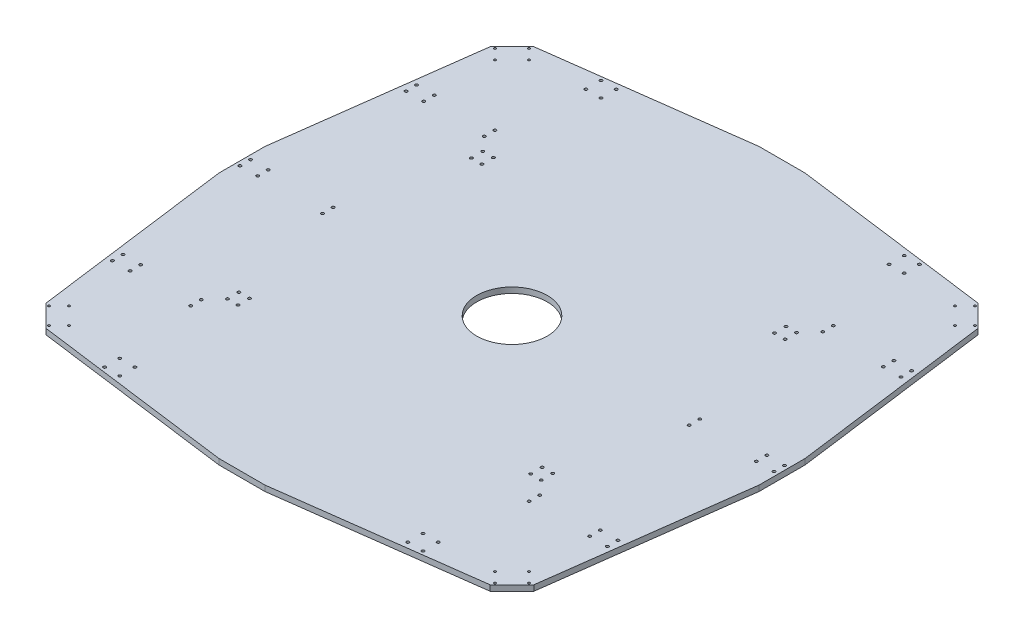
SolidWorks part; units mm, degrees
ref_plane "前视基准面" through (0, 0, 0) normal (0, 0, 1) x (1, 0, 0)
ref_plane "上视基准面" through (0, 0, 0) normal (0, 1, 0) x (1, 0, 0)
ref_plane "右视基准面" through (0, 0, 0) normal (1, 0, 0) x (0, 0, -1)
other "Configuration Table"
sketch "草图1" plane through (0, 0, 0) normal (0, 1, 0) x (1, 0, 0)
  line L0 (-314.9222, 345.9222) -> (-345.9222, 314.9222)
  line L5 (325, -325) -> (-325, 325) construction
  line L6 (325, 325) -> (-325, -325) construction
  line L7 (0, 325) -> (0, -325) construction
  line L8 (-325, 0) -> (325, 0) construction
  line L9 (314.9222, 345.9222) -> (32.7201, 383.0748)
  line L10 (314.9222, 345.9222) -> (345.9222, 314.9222)
  line L12 (-314.9222, 345.9222) -> (-32.7201, 383.0748)
  line L13 (0, 325) -> (0, 399.6983)
  line L14 (-32.7201, 383.0748) -> (32.7201, 383.0748)
  line L15 (314.9222, -345.9222) -> (32.7201, -383.0748)
  line L16 (-32.7201, -383.0748) -> (32.7201, -383.0748)
  line L17 (-314.9222, -345.9222) -> (-32.7201, -383.0748)
  line L18 (-314.9222, -345.9222) -> (-345.9222, -314.9222)
  line L19 (-345.9222, 314.9222) -> (-383.0748, 32.7201)
  line L20 (-383.0748, -32.7201) -> (-383.0748, 32.7201)
  line L21 (-345.9222, -314.9222) -> (-383.0748, -32.7201)
  line L22 (-345.9222, -314.9222) -> (-314.9222, -345.9222)
  line L23 (345.9222, -314.9222) -> (314.9222, -345.9222)
  line L24 (345.9222, -314.9222) -> (383.0748, -32.7201)
  line L25 (383.0748, 32.7201) -> (383.0748, -32.7201)
  line L26 (345.9222, 314.9222) -> (383.0748, 32.7201)
  line L27 (-337.8712, -313.8296) -> (-342.443, -318.4014)
  line L28 (-314.9222, -345.9222) -> (-293.6978, -324.6978)
  line L29 (-326.1795, -302.1379) -> (-298.6587, -329.6587)
  line L30 (-345.9222, -314.9222) -> (-325, -294)
  line L31 (-326.1795, -302.1379) -> (-329.6587, -298.6587)
  line L32 (-313.4871, -289.4455) -> (-337.8712, -313.8296)
  line L33 (-289.4455, -313.4871) -> (-313.8296, -337.8712)
  line L34 (-313.8296, -337.8712) -> (-318.4014, -342.443)
  circle A1 centre (-326.1795, -302.1379) radius 1.5
  circle A2 centre (-302.1379, -326.1795) radius 1.5
  circle A3 centre (-340.3217, -316.28) radius 1.5
  circle A4 centre (-316.28, -340.3217) radius 1.5
  circle A5 centre (0, 0) radius 50
  circle A6 centre (325.9184, 215.682) radius 2
  circle A7 centre (377.0748, 9.4052) radius 2
  circle A8 centre (350.9184, 215.682) radius 2
  circle A9 centre (325.9184, 200.682) radius 2
  circle A10 centre (350.9184, 200.682) radius 2
  circle A11 centre (352.0748, 9.4052) radius 2
  circle A12 centre (352.0748, -5.5948) radius 2
  circle A13 centre (377.0748, -5.5948) radius 2
  circle A14 centre (325.9184, -200.682) radius 2
  circle A15 centre (350.9184, -200.682) radius 2
  circle A16 centre (325.9184, -215.682) radius 2
  circle A17 centre (350.9184, -215.682) radius 2
  circle A18 centre (-350.9184, -200.682) radius 2
  circle A19 centre (-325.9184, -200.682) radius 2
  circle A20 centre (-350.9184, -215.682) radius 2
  circle A21 centre (-325.9184, -215.682) radius 2
  circle A22 centre (-377.0748, 6.2425) radius 2
  circle A23 centre (-352.0748, 6.2425) radius 2
  circle A24 centre (-377.0748, -8.7575) radius 2
  circle A25 centre (-352.0748, -8.5322) radius 2
  circle A26 centre (-350.9184, 215.682) radius 2
  circle A27 centre (-325.9184, 215.682) radius 2
  circle A28 centre (-350.9184, 200.682) radius 2
  circle A29 centre (-325.9184, 200.682) radius 2
  circle A30 centre (-222.5, 181.0301) radius 2
  circle A31 centre (-207.5, 181.0301) radius 2
  circle A32 centre (-222.5, 164.8255) radius 2
  circle A33 centre (-207.5, 164.8255) radius 2
  circle A34 centre (-207.5, -164.8255) radius 2
  circle A35 centre (-222.5, -164.8255) radius 2
  circle A36 centre (-207.5, -181.0301) radius 2
  circle A37 centre (-222.5, -181.0301) radius 2
  circle A38 centre (207.5, 164.8255) radius 2
  circle A39 centre (222.5, 164.8255) radius 2
  circle A40 centre (207.5, 181.0301) radius 2
  circle A41 centre (222.5, 181.0301) radius 2
  circle A42 centre (207.5, -181.0301) radius 2
  circle A43 centre (207.5, -164.8255) radius 2
  circle A44 centre (222.5, -181.0301) radius 2
  circle A45 centre (222.5, -164.8255) radius 2
  circle A46 centre (-240, 215.682) radius 2
  circle A47 centre (-240, 200.682) radius 2
  circle A48 centre (-260, 6.2425) radius 2
  circle A49 centre (-260, -8.7575) radius 2
  circle A50 centre (-240, -215.682) radius 2
  circle A51 centre (-240, -200.682) radius 2
  circle A52 centre (240, 215.682) radius 2
  circle A53 centre (240, 200.682) radius 2
  circle A54 centre (260, 6.2425) radius 2
  circle A55 centre (260, -8.7575) radius 2
  circle A56 centre (240, -200.682) radius 2
  circle A57 centre (240, -215.682) radius 2
  point P0 (0, 0)
  point P13 (0, 383.0748)
  point P24 (-330.4222, -330.4222)
  point P44 (-326.1795, -302.1379)
  point P45 (-302.1379, -326.1795)
  dimension "D6" = 3
  dimension "D7" = 20
  dimension "D8" = 100
  dimension "D1" = 650
  dimension "D2" = 650
  dimension "D3" = 31
  dimension "D4" = 142.5
  dimension "D5" = 17
extrude "凸台-拉伸2" add sketch "草图1" along normal blind 8 contours L26 L10 L9 L14 L12 L0 L19 L20 L21 L18 L17 L16 L15 L23 L24 L25 | A2 L29 A1 L32 L27 L22 L34 L33 | A1 L31 L30 L22 L27 L32 | A2 L33 L34 L18 L28 L29 region at (-172.4069, 0, -353.7562) region at (-336.0431, 0, 308.3956) region at (-322.2706, 0, 322.2706) region at (-308.3956, 0, 336.0431)
sketch "草图2" plane through (0, 8, 0) normal (0, 1, 0) x (1, 0, 0)
  line L0 (0, 0) -> (-330.4222, -330.4222) construction
pattern_circular "阵列(圆周)1" count 4 over 360 about axis through (0, 8, 0) along (0, 1, 0) of face at (-326.1795, 8, 303.6379) of face at (-340.3217, 8, 317.78) of face at (-302.1379, 8, 327.6795) of face at (-316.28, 8, 341.8217)
sketch "草图3" plane through (0, 8, 0) normal (0, 1, 0) x (1, 0, 0)
  line L0 (383.0748, 0) -> (-381.6237, 0)
  line L1 (383.0748, 32.7201) -> (383.0748, -32.7201) construction
  circle A0 centre (-225.7527, 352.0186) radius 2
  circle A1 centre (-204.2473, 352.0186) radius 2
  circle A2 centre (-225.7527, 330.5131) radius 2
  circle A3 centre (-204.2473, 330.5131) radius 2
  circle A4 centre (204.2473, 352.0186) radius 2
  circle A5 centre (225.7527, 352.0186) radius 2
  circle A6 centre (204.2473, 330.5131) radius 2
  circle A7 centre (225.7429, 330.3998) radius 2
  circle A8 centre (225.7429, -330.3998) radius 2
  circle A9 centre (204.2473, -330.5131) radius 2
  circle A10 centre (225.7527, -352.0186) radius 2
  circle A11 centre (204.2473, -352.0186) radius 2
  circle A12 centre (-204.2473, -330.5131) radius 2
  circle A13 centre (-225.7527, -330.5131) radius 2
  circle A14 centre (-204.2473, -352.0186) radius 2
  circle A15 centre (-225.7527, -352.0186) radius 2
  dimension "D1" = 4
extrude "切除-拉伸1" cut sketch "草图3" against normal blind 55 and the other way blind 37 contours A13 | A15 | A12 | A14 | A10 | A9 | A11 | A8 | A2 | A0 | A3 | A1 | A7 | A5 | A6 | A4 region at (-225.7527, 8, -352.0186) region at (-204.2473, 8, -352.0186) region at (-225.7527, 8, -330.5131) region at (-204.2473, 8, -330.5131) region at (204.2473, 8, -352.0186) region at (225.7527, 8, -352.0186) region at (204.2473, 8, -330.5131) region at (225.7429, 8, -330.3998) region at (225.7429, 8, 330.3998) region at (204.2473, 8, 330.5131) region at (225.7527, 8, 352.0186) region at (204.2473, 8, 352.0186) region at (-204.2473, 8, 330.5131) region at (-225.7527, 8, 330.5131) region at (-204.2473, 8, 352.0186) region at (-225.7527, 8, 352.0186)
